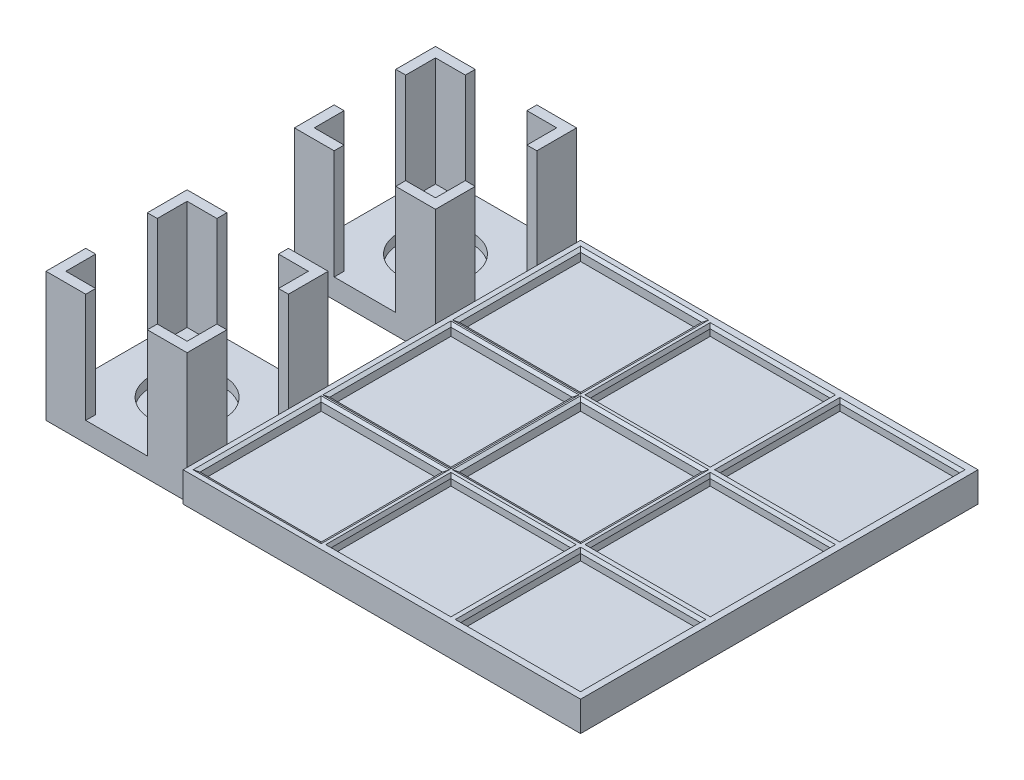
SolidWorks part; units mm, degrees
note: The reader was unsure of these and kept them because the rebuilt part matched: shared geometry of "Sketch1<6>", "Sketch1<8>".
ref_plane "Front Plane" through (0, 0, 0) normal (0, 0, 1) x (1, 0, 0)
ref_plane "Top Plane" through (0, 0, 0) normal (0, 1, 0) x (1, 0, 0)
ref_plane "Right Plane" through (0, 0, 0) normal (1, 0, 0) x (0, 0, -1)
sketch "Sketch1" plane through (0, 0, 0) normal (0, 1, 0) x (1, 0, 0)
  line L0 (100, 200) -> (100, 195.75) construction
  line L1 (0, 0) -> (200, 0)
  line L2 (0, 0) -> (0, 200)
  line L3 (0, 200) -> (200, 200)
  line L4 (200, 0) -> (200, 200)
  line L9 (4.25, 195.75) -> (65.25, 195.75)
  line L10 (4.25, 195.75) -> (4.25, 134.75)
  line L11 (4.25, 134.75) -> (65.25, 134.75)
  line L12 (65.25, 195.75) -> (65.25, 134.75)
  line L13 (69.5, 195.75) -> (130.5, 195.75)
  line L14 (69.5, 195.75) -> (69.5, 134.75)
  line L15 (69.5, 134.75) -> (130.5, 134.75)
  line L16 (130.5, 195.75) -> (130.5, 134.75)
  line L17 (134.75, 195.75) -> (195.75, 195.75)
  line L18 (134.75, 195.75) -> (134.75, 134.75)
  line L19 (134.75, 134.75) -> (195.75, 134.75)
  line L20 (195.75, 195.75) -> (195.75, 134.75)
  line L21 (4.25, 130.5) -> (65.25, 130.5)
  line L22 (4.25, 130.5) -> (4.25, 69.5)
  line L23 (4.25, 69.5) -> (65.25, 69.5)
  line L24 (65.25, 130.5) -> (65.25, 69.5)
  line L25 (69.5, 130.5) -> (130.5, 130.5)
  line L26 (69.5, 130.5) -> (69.5, 69.5)
  line L27 (69.5, 69.5) -> (130.5, 69.5)
  line L28 (130.5, 130.5) -> (130.5, 69.5)
  line L29 (134.75, 130.5) -> (195.75, 130.5)
  line L30 (134.75, 130.5) -> (134.75, 69.5)
  line L31 (134.75, 69.5) -> (195.75, 69.5)
  line L32 (195.75, 130.5) -> (195.75, 69.5)
  line L33 (4.25, 65.25) -> (65.25, 65.25)
  line L34 (4.25, 65.25) -> (4.25, 4.25)
  line L35 (4.25, 4.25) -> (65.25, 4.25)
  line L36 (65.25, 65.25) -> (65.25, 4.25)
  line L37 (69.5, 65.25) -> (130.5, 65.25)
  line L38 (69.5, 65.25) -> (69.5, 4.25)
  line L39 (69.5, 4.25) -> (130.5, 4.25)
  line L40 (130.5, 65.25) -> (130.5, 4.25)
  line L41 (134.75, 65.25) -> (195.75, 65.25)
  line L42 (134.75, 65.25) -> (134.75, 4.25)
  line L43 (134.75, 4.25) -> (195.75, 4.25)
  line L44 (195.75, 65.25) -> (195.75, 4.25)
  line L45 (100, 134.75) -> (100, 130.5) construction
  line L46 (100, 69.5) -> (100, 65.25) construction
  line L47 (100, 4.25) -> (100, 0) construction
  line L48 (4.25, 100) -> (0, 100) construction
  line L49 (69.5, 100) -> (65.25, 100) construction
  line L50 (130.5, 100) -> (134.75, 100) construction
  line L51 (195.75, 100) -> (200, 100) construction
  line L68 (0, 200) -> (0.0022, 198)
  line L80 (0, 200) -> (0, 0)
  line L81 (0, 0) -> (0, 2)
  line L86 (0, 200) -> (0, 198)
  line L87 (-5, 193) -> (0, 193) construction
  line L92 (0, 2) -> (-71, 2)
  line L93 (0, 2) -> (0, 73)
  line L94 (0, 73) -> (-71, 73)
  line L95 (-71, 2) -> (-71, 73)
  line L96 (-5, 7) -> (-66, 7)
  line L97 (-5, 7) -> (-5, 68)
  line L98 (-5, 68) -> (-66, 68)
  line L99 (-66, 7) -> (-66, 68)
  line L100 (0, 198) -> (-71, 198)
  line L101 (0, 198) -> (0, 127)
  line L102 (0, 127) -> (-71, 127)
  line L103 (-71, 198) -> (-71, 127)
  line L104 (-66, 193) -> (-5, 193)
  line L105 (-66, 193) -> (-66, 132)
  line L106 (-66, 132) -> (-5, 132)
  line L107 (-5, 193) -> (-5, 132)
  line L108 (-5, 193) -> (-5, 198) construction
  line L109 (-5, 7) -> (-5, 2) construction
  line L110 (-5, 7) -> (0, 7) construction
  line L111 (-66, 68) -> (-66, 73) construction
  line L112 (-66, 68) -> (-71, 68) construction
  line L113 (-66, 132) -> (-66, 127) construction
  line L114 (-66, 132) -> (-71, 132) construction
  line L115 (-66, 53) -> (-71, 53)
  line L116 (-51, 68) -> (-51, 73)
  line L117 (-66, 22) -> (-71, 22)
  line L118 (-51, 7) -> (-51, 2)
  line L119 (-20, 7) -> (-20, 2)
  line L120 (-5, 22) -> (0, 22)
  line L121 (-20, 73) -> (-20, 68)
  line L122 (-5, 53) -> (0, 53)
  line L123 (-66, 70.5) -> (-51, 70.5) construction
  line L124 (-68.5, 68) -> (-68.5, 53) construction
  line L125 (-2.5, 22) -> (-2.5, 7) construction
  line L126 (-5, 4.5) -> (-20, 4.5) construction
  line L127 (-66, 178) -> (-71, 178)
  line L128 (-51, 193) -> (-51, 198)
  line L129 (-20, 193) -> (-20, 198)
  line L130 (-5, 178) -> (0, 178)
  line L131 (-5, 147) -> (0, 147)
  line L132 (-20, 132) -> (-20, 127)
  line L133 (-51, 132) -> (-51, 127)
  line L134 (-66, 129.5) -> (-51, 129.5) construction
  line L135 (-66, 147) -> (-71, 147)
  line L136 (-68.5, 147) -> (-68.5, 132) construction
  line L137 (-5, 195.5) -> (-20, 195.5) construction
  line L138 (-2.5, 193) -> (-2.5, 178) construction
  point P79 (0, 100)
  dimension "D1" = 200
  dimension "D2" = 2
  dimension "D3" = 61
  dimension "D4" = 5
  dimension "D5" = 15
extrude "BoardBase" add sketch "Sketch1" along normal blind 10
extrude "PieceHolders" add sketch "Sketch1<6>" along normal blind 15 contours L1 L4 L3 L2 L9 L12 L11 L10 L13 L16 L15 L14 L17 L20 L19 L18 L21 L24 L23 L22 L25 L28 L27 L26 L29 L32 L31 L30 L33 L36 L35 L34 L37 L40 L39 L38 L41 L44 L43 L42
sketch "Sketch1<6>" plane through (0, 0, 0) normal (0, 1, 0) x (1, 0, 0) same geometry as "Sketch1"
chamfer "PieceSlideAid" distance 1 angle 60 36 edges at (65.25, 15, -165.25) (34.75, 15, -134.75) (4.25, 15, -165.25) (34.75, 15, -195.75) (130.5, 15, -165.25) (100, 15, -195.75) (69.5, 15, -165.25) (100, 15, -134.75) (100, 15, -69.5) (69.5, 15, -100) (130.5, 15, -100) (100, 15, -130.5) (134.75, 15, -165.25) (165.25, 15, -195.75) (195.75, 15, -165.25) (165.25, 15, -134.75) (195.75, 15, -100) (165.25, 15, -69.5) (165.25, 15, -130.5) (134.75, 15, -100) (195.75, 15, -34.75) (165.25, 15, -65.25) (134.75, 15, -34.75) (165.25, 15, -4.25) (100, 15, -4.25) (130.5, 15, -34.75) (100, 15, -65.25) (69.5, 15, -34.75) (34.75, 15, -4.25) (65.25, 15, -34.75) (4.25, 15, -34.75) (34.75, 15, -65.25) (34.75, 15, -69.5) (4.25, 15, -100) (34.75, 15, -130.5) (65.25, 15, -100)
extrude "Boss-Extrude3" add sketch "Sketch1<8>" along normal blind 65 contours L105 L135 L103 L102 L133 L106 | L104 L128 L100 L103 L127 L105 | L107 L130 L101 L100 L129 L104 | L106 L132 L102 L80 L131 L107 | L98 L116 L94 L95 L115 L99 | L118 L96 L99 L117 L95 L92 | L120 L97 L96 L119 L92 L80 | L97 L122 L80 L94 L121 L98
sketch "Sketch1<8>" plane through (0, 0, 0) normal (0, 1, 0) x (1, 0, 0) same geometry as "Sketch1"
sketch "Sketch4" plane through (0, 10, 0) normal (0, 1, 0) x (1, 0, 0)
  line L0 (-71, 37.5) -> (0, 37.5) construction
  line L1 (-71, 22) -> (-71, 53) construction
  line L2 (0, 53) -> (0, 22) construction
  line L3 (-71, 162.5) -> (0, 162.5) construction
  line L5 (0, 147) -> (0, 178) construction
  line L6 (-71, 178) -> (-71, 147) construction
  circle A0 centre (-35.5, 37.5) radius 18.5
  circle A1 centre (-35.5, 162.5) radius 18.5
  point P2 (0, 0)
  point P13 (0, 0)
  point P14 (-62.7798, 162.5)
  point P15 (0, 0)
  point P16 (0, 0)
  point P19 (0, 0)
  dimension "D1" = 37
extrude "Cut-Extrude1" cut sketch "Sketch4" against normal blind 5
